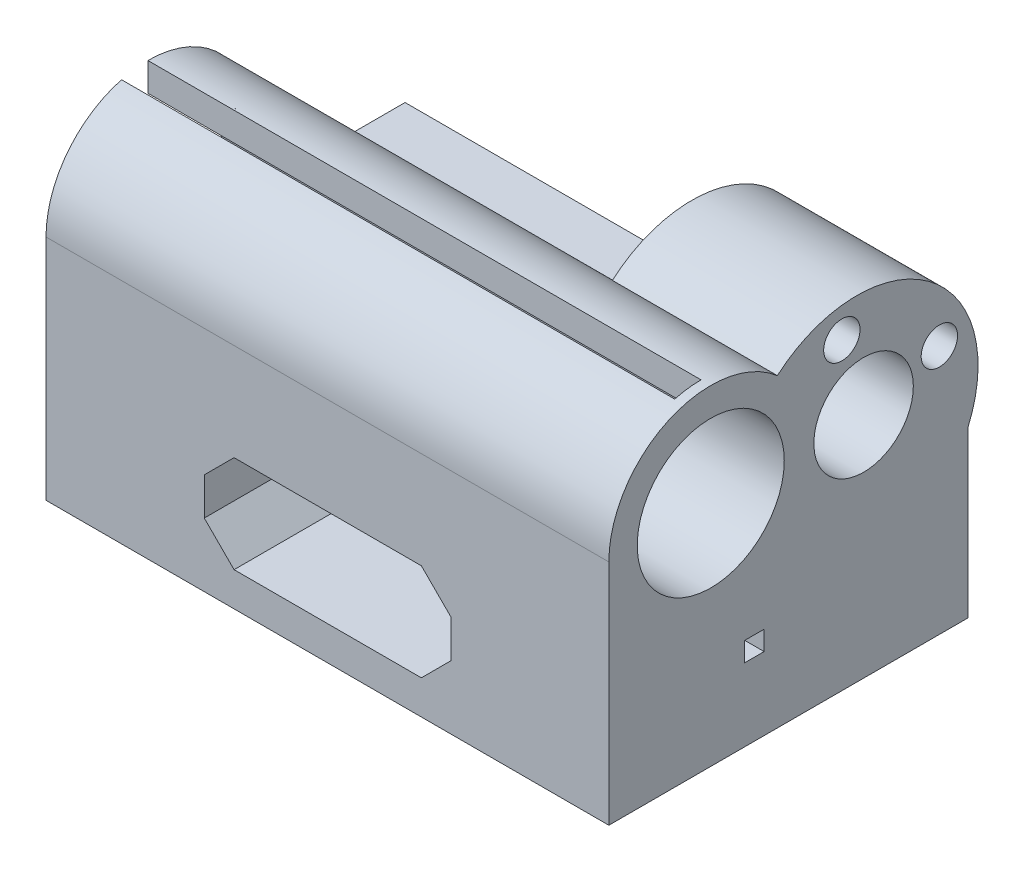
SolidWorks part; units mm, degrees
ref_plane "Front Plane" through (0, 0, 0) normal (0, 0, 1) x (1, 0, 0)
ref_plane "Top Plane" through (0, 0, 0) normal (0, 1, 0) x (1, 0, 0)
ref_plane "Right Plane" through (0, 0, 0) normal (1, 0, 0) x (0, 0, -1)
sketch "Sketch2" plane through (0, 0, 0) normal (0, 1, 0) x (1, 0, 0)
  line L1 (-29, -18.5) -> (29, -18.5)
  line L2 (-29, -18.5) -> (-29, 18.5)
  line L3 (-29, 18.5) -> (29, 18.5)
  line L4 (29, -18.5) -> (29, 18.5)
  line L5 (-29, -18.5) -> (29, 18.5) construction
  line L6 (-29, 18.5) -> (29, -18.5) construction
  point P0 (0, 0)
  dimension "D1" = 58
  dimension "D2" = 37
extrude "Boss-Extrude1" add sketch "Sketch2" along normal blind 17
sketch "Sketch3" plane through (29, 0, 0) normal (1, 0, 0) x (0, 0, -1)
  line L0 (-18.5, 0) -> (18.5, 0) construction
  line L1 (-18.5, 23.5) -> (-18.5, 17)
  line L2 (-18.5, 17) -> (-18.5, 0) construction
  line L5 (2.5, 23.5) -> (2.5, 17)
  line L6 (-18.5, 17) -> (18.5, 17) construction
  line L7 (-18.5, 17) -> (2.5, 17)
  arc A0 (2.5, 23.5) -> (-18.5, 23.5) centre (-8, 23.5) ccw
  dimension "D2" = 21
  dimension "D4" = 23.5
  dimension "D5" = 10.5
extrude "Boss-Extrude2" add sketch "Sketch3" against normal up to surface (58 mm away) up to face at (-29, 8.5, 0)
sketch "Sketch4" plane through (29, 0, 0) normal (1, 0, 0) x (0, 0, -1)
  line L1 (-18.5, 0) -> (18.5, 0) construction
  circle A0 centre (7.0436, 22) radius 12.5
  dimension "D1" = 25
  dimension "D2" = 22
extrude "Boss-Extrude3" add sketch "Sketch4" against normal blind 17
sketch "Sketch5" plane through (0, 0, -18.5) normal (0, 0, -1) x (-1, 0, 0)
  line L0 (-12.75, 6.57) -> (-12.75, 10.427)
  line L1 (-12.75, 10.427) -> (-9.68, 13.497)
  line L2 (-9.68, 13.497) -> (9.62, 13.497)
  line L3 (9.62, 13.497) -> (12.69, 10.427)
  line L4 (12.69, 10.427) -> (12.69, 6.57)
  line L5 (12.69, 6.57) -> (9.62, 3.5)
  line L6 (9.62, 3.5) -> (-9.68, 3.5)
  line L7 (-9.68, 3.5) -> (-12.75, 6.57)
  line L8 (-29, 0) -> (29, 0) construction
  line L9 (-29, 17) -> (-29, 0) construction
  dimension "D1" = 3.857
  dimension "D2" = 3.857
  dimension "D3" = 135
  dimension "D4" = 135
  dimension "D5" = 3.07
  dimension "D6" = 3.07
  dimension "D7" = 3.07
  dimension "D8" = 3.07
  dimension "D9" = 19.3
  dimension "D10" = 3.5
  dimension "D11" = 16.25
extrude "Cut-Extrude1" cut sketch "Sketch5" against normal through all
sketch "Sketch6" plane through (0, 0, -18.5) normal (0, 0, -1) x (-1, 0, 0)
  line L0 (-29, 0) -> (29, 0) construction
  line L1 (-29, 17) -> (-29, 0) construction
  circle A0 centre (-23, 8.5) radius 4.076
  circle A1 centre (22, 8.5) radius 4.076
  dimension "D5" = 8.152
  dimension "D6" = 8.152
  dimension "D1" = 8.5
  dimension "D2" = 8.5
  dimension "D3" = 6
  dimension "D4" = 51
extrude "Cut-Extrude2" cut sketch "Sketch6" against normal blind 23
sketch "Sketch7" plane through (29, 0, 0) normal (1, 0, 0) x (0, 0, -1)
  line L0 (-18.5, 23.5) -> (-18.5, 0) construction
  line L1 (-18.5, 0) -> (18.5, 0) construction
  circle A0 centre (-8, 23.5) radius 7.575
  circle A1 centre (7.7501, 23.5) radius 5.125
  dimension "D1" = 10.25
  dimension "D2" = 15.15
  dimension "D3" = 26.2501
  dimension "D4" = 23.5
extrude "Cut-Extrude3" cut sketch "Sketch7" against normal through all
sketch "Sketch8" plane through (29, 0, 0) normal (1, 0, 0) x (0, 0, -1)
  line L0 (7.7501, 23.5) -> (5.5097, 31.31) construction
  line L3 (7.7501, 23.5) -> (15.5601, 25.7405) construction
  line L4 (5.5097, 31.31) -> (6.0267, 29.5077) construction
  line L7 (15.5601, 25.7405) -> (13.7578, 25.2235) construction
  circle A1 centre (5.5097, 31.31) radius 1.875
  circle A2 centre (15.5601, 25.7405) radius 1.875
  dimension "D1" = 3.75
  dimension "D2" = 6.25
  dimension "D3" = 3.75
  dimension "D7" = 6.25
extrude "Cut-Extrude4" cut sketch "Sketch8" against normal through all
sketch "Sketch12" plane through (-29, 0, 0) normal (-1, 0, 0) x (0, 0, 1)
  line L0 (-18.5, 17) -> (-18.5, 0) construction
  line L1 (4.5, 7.5) -> (2.5, 7.5)
  line L2 (4.5, 7.5) -> (4.5, 9.5)
  line L3 (4.5, 9.5) -> (2.5, 9.5)
  line L4 (2.5, 7.5) -> (2.5, 9.5)
  line L5 (-18.5, 0) -> (18.5, 0) construction
  dimension "D1" = 23
  dimension "D2" = 2
  dimension "D3" = 2
  dimension "D4" = 7.5
extrude "Cut-Extrude6" cut sketch "Sketch12" against normal blind 8
mirror "Mirror1" about plane through (0, 0, 0) normal (1, 0, 0) of "Cut-Extrude6"
sketch "Sketch13" plane through (-29, 0, 0) normal (-1, 0, 0) x (0, 0, 1)
  line L0 (8, 23.5) -> (10.7176, 33.6422) construction
  line L1 (8, 23.5) -> (-2.5, 23.5) construction
  line L2 (8, 23.5) -> (8, 34) construction
  line L3 (9.9606, 30.8169) -> (10.7176, 33.6422)
  line L4 (8, 34) -> (8, 31.075)
  arc A0 (9.9606, 30.8169) -> (8, 31.075) centre (8, 23.5) ccw
  arc A1 (-2.5, 23.5) -> (8, 34) centre (8, 23.5) ccw
  arc A2 (18.5, 23.5) -> (-2.5, 23.5) centre (8, 23.5) ccw construction
  arc A3 (1.1397, 31.449) -> (-2.5, 23.5) centre (8, 23.5) ccw construction
  circle A4 centre (8, 23.5) radius 7.575 construction
  circle M5 centre (8, 23.5) radius 7.575
  arc M8 (18.5, 23.5) -> (-2.5, 23.5) centre (8, 23.5) ccw
  dimension "D1" = 15
  dimension "D2" = 90
extrude "Cut-Extrude7" cut sketch "Sketch13" against normal blind 57 contours L4 L3 M8 M5 region at (-29, 32.5126, 9.1865)
sketch "Sketch14" plane through (0, 0, 0) normal (0, -1, 0) x (1, 0, 0)
  line L0 (0, -11.5) -> (29, -11.5) construction
  line L1 (29, 18.5) -> (29, -18.5) construction
  line L2 (0, -11.5) -> (0, -18.5) construction
  line L3 (29, -18.5) -> (-29, -18.5) construction
  circle A0 centre (0, -11.5) radius 1.5
  dimension "D1" = 3
  dimension "D2" = 7
  dimension "D3" = 29
extrude "Cut-Extrude8" cut sketch "Sketch14" against normal through all
